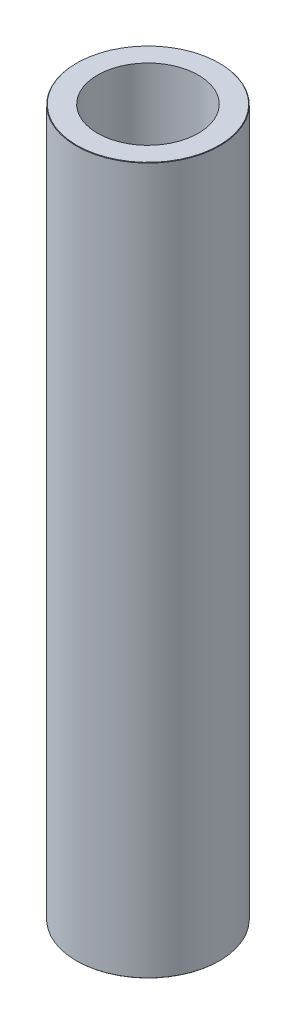
SolidWorks part; units mm, degrees
ref_plane "Front Plane" through (0, 0, 0) normal (0, 0, 1) x (1, 0, 0)
ref_plane "Top Plane" through (0, 0, 0) normal (0, 1, 0) x (1, 0, 0)
ref_plane "Right Plane" through (0, 0, 0) normal (1, 0, 0) x (0, 0, -1)
sketch "Sketch1" plane through (0, 0, 0) normal (0, 1, 0) x (1, 0, 0)
  circle A0 centre (0, 0) radius 50
  dimension "SHAFT_OD" = 100
extrude "Boss-Extrude1" add sketch "Sketch1" along normal blind 493.0053
sketch "Sketch2" plane through (0, 0, 0) normal (0, 1, 0) x (1, 0, 0)
  circle A0 centre (0, 0) radius 35.1975
  dimension "BORE_D" = 70.395
extrude "Cut-Extrude1" cut sketch "Sketch2" along normal through all
chamfer "Chamfer1" distance 0.2822 angle 45 2 edges at (0, 493.0053, 50) (0, 0, 50)
